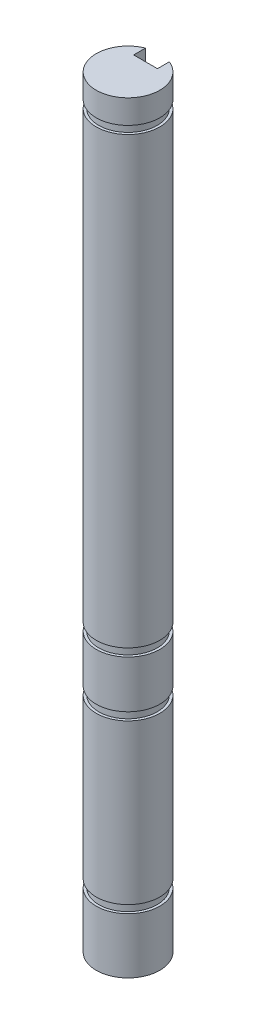
SolidWorks part; units mm, degrees
note: The reader was unsure of these and kept them because the rebuilt part matched: shared geometry of "Sketch3<5>", "Sketch3<6>".
material "1023 Carbon Steel Sheet (SS)"
ref_plane "Front Plane" through (0, 0, 0) normal (0, 0, 1) x (1, 0, 0)
ref_plane "Top Plane" through (0, 0, 0) normal (0, 1, 0) x (1, 0, 0)
ref_plane "Right Plane" through (0, 0, 0) normal (1, 0, 0) x (0, 0, -1)
sketch "Sketch1" plane through (0, 0, 0) normal (0, 1, 0) x (1, 0, 0)
  line L0 (-1.1906, 2.9433) -> (-1.1906, 1.7527)
  line L1 (-1.1906, 1.7527) -> (1.1906, 1.7527)
  line L2 (1.1906, 1.7527) -> (1.1906, 2.9433)
  arc A0 (-1.1906, 2.9433) -> (1.1906, 2.9433) centre (0, 0) ccw
  point P5 (0, 1.7527)
  dimension "D1" = 6.35
  dimension "D2" = 2.3813
  dimension "D3" = 1.1906
extrude "Boss-Extrude1" add sketch "Sketch1" along normal blind 76.2
sketch "Sketch2" plane through (0, 76.2, 0) normal (0, 1, 0) x (1, 0, 0)
  circle A0 centre (0, 0) radius 2.921
  arc A1 (-1.1906, 2.9433) -> (1.1906, 2.9433) centre (0, 0) ccw construction
  circle A2 centre (0, 0) radius 3.175
  dimension "D1" = 0.254
extrude "Cut-Extrude1" cut sketch "Sketch2" along normal blind 0.7874 from offset 3.175 offset against normal yes
sketch "Sketch3" plane through (0, 0, 0) normal (0, -1, 0) x (1, 0, 0)
  circle A0 centre (0, 0) radius 2.921
  circle A2 centre (0, 0) radius 3.175
extrude "Cut-Extrude2" cut sketch "Sketch3" along normal blind 0.7874 from offset 6.35 offset against normal yes
extrude "Cut-Extrude3" cut sketch "Sketch3<5>" along normal blind 0.7874 from offset 23.0441 offset against normal yes
sketch "Sketch3<5>" plane through (0, 0, 0) normal (0, -1, 0) x (1, 0, 0) same geometry as "Sketch3"
extrude "Cut-Extrude4" cut sketch "Sketch3<6>" along normal blind 0.7874 from offset 28.575
sketch "Sketch3<6>" plane through (0, 0, 0) normal (0, -1, 0) x (1, 0, 0) same geometry as "Sketch3"
